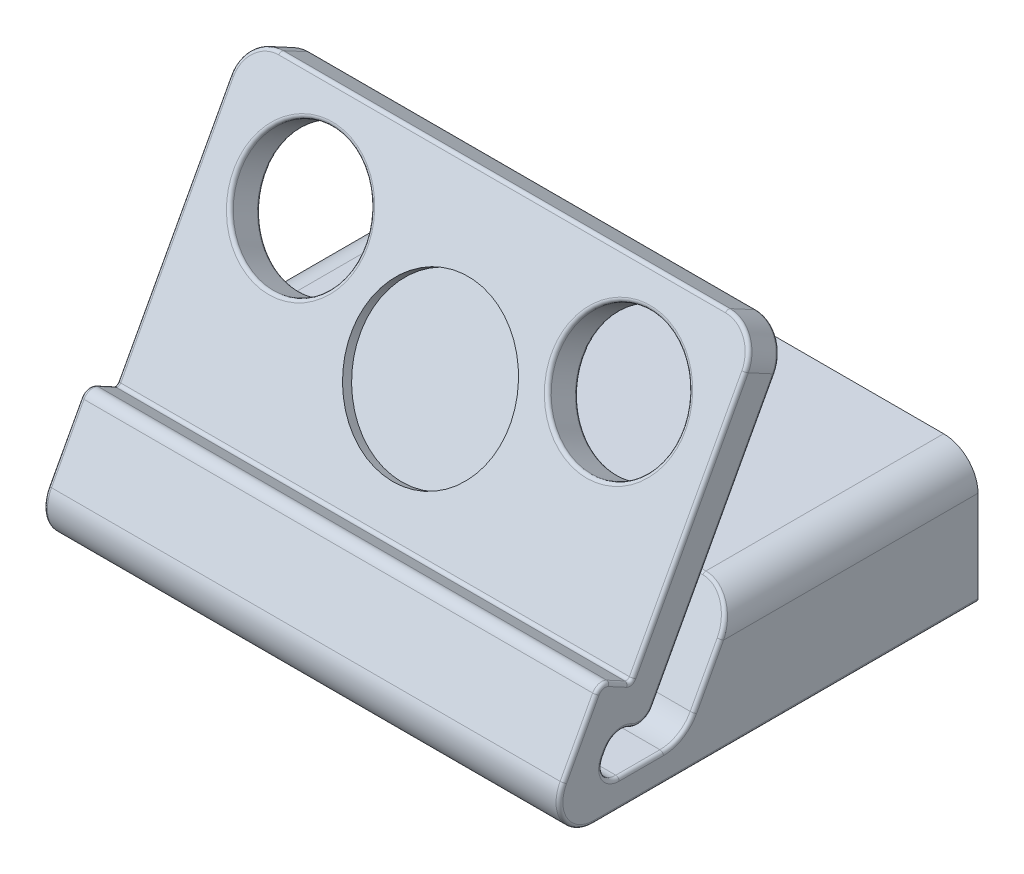
SolidWorks part; units mm, degrees
ref_plane "Front Plane" through (0, 0, 0) normal (0, 0, 1) x (1, 0, 0)
ref_plane "Top Plane" through (0, 0, 0) normal (0, 1, 0) x (1, 0, 0)
ref_plane "Right Plane" through (0, 0, 0) normal (1, 0, 0) x (0, 0, -1)
sketch "Sketch2" plane through (0, 0, 0) normal (1, 0, 0) x (0, 0, -1)
  line L0 (68.9, -29.4084) -> (-59.6419, -29.4084)
  line L1 (-59.6419, -29.4084) -> (-40.8213, 5.5155)
  line L3 (5.934, 71.1961) -> (-32.0182, 0.7714)
  line L4 (-43.865, -21.2117) -> (-16.6838, -21.2117)
  line L5 (-16.6838, -21.2117) -> (-0.8623, 8.147)
  line L6 (-0.8623, 8.147) -> (68.9, 8.147)
  line L7 (68.9, 8.147) -> (68.9, -29.4084)
  line L8 (5.934, 71.1961) -> (14.7371, 66.4521)
  line L9 (14.7371, 66.4521) -> (-27.9592, -12.7757)
  line L10 (-27.9592, -12.7757) -> (-36.7622, -8.0316)
  line L11 (-40.8213, 5.5155) -> (-32.0182, 0.7714)
  line L12 (-36.7622, -8.0316) -> (-43.865, -21.2117)
  dimension "D1" = 10
  dimension "D2" = 10
  dimension "D3" = 10
  dimension "D4" = 80
extrude "Boss-Extrude1" add sketch "Sketch2" against normal blind 150
fillet "Fillet1" radius 10 6 edges at (-150, 8.147, -34.0188) (0, 8.147, -34.0188) (-75, -29.4084, 59.6419) (-150, 68.8241, -10.3355) (0, 68.8241, -10.3355) (-75, -21.2117, 16.6838)
fillet "Fillet2" radius 5 3 edges at (-75, -12.7757, 27.9592) (-75, -8.0316, 36.7622) (-75, -21.2117, 43.865)
fillet "Fillet3" radius 3 1 edges at (-75, 5.5155, 40.8213)
sketch "Sketch3" plane through (0, 13.5451, 25.1344) normal (0, 0.4744, 0.8803) x (1, 0, 0)
  line L0 (-75, 65.4896) -> (-75, -14.5104) construction
  line L1 (-140, 65.4896) -> (-10, 65.4896) construction
  line L2 (-150, -14.5104) -> (0, -14.5104) construction
  circle A0 centre (-75, 20.4896) radius 23.1387
  circle A1 centre (-121.2579, 38.3022) radius 18.5
  circle A2 centre (-28.7421, 38.3022) radius 18.5
extrude "Cut-Extrude1" cut sketch "Sketch3" against normal blind 20 contours A1 | A2 region at (-121.2579, 47.2628, 6.9638) region at (-28.7421, 47.2628, 6.9638)
extrude "Cut-Extrude2" cut sketch "Sketch3<3>" against normal blind 3 contours L0 A0 | A0 L0 region at (-65.1796, 31.5822, 15.4141) region at (-84.8204, 31.5822, 15.4141)
sketch "Sketch3<3>" plane through (0, 13.5451, 25.1344) normal (0, 0.4744, 0.8803) x (1, 0, 0) same geometry as "Sketch3"
ref_plane "Plane1" through (0, 13.0707, 24.2541) normal (0, 0.4744, 0.8803) x (1, 0, 0)
sketch "Sketch4" plane through (0, 13.0707, 24.2541) normal (0, 0.4744, 0.8803) x (1, 0, 0)
  circle A0 centre (-28.7421, 38.3022) radius 18.5 construction
  circle A2 centre (-28.7421, 38.3022) radius 18.5
  circle A4 centre (-121.2579, 38.3022) radius 18.5 construction
  circle A5 centre (-121.2579, 38.3022) radius 18.5
sketch "Sketch5" plane through (0, -29.4084, 0) normal (0, -1, 0) x (1, 0, 0)
  line L1 (-144.1476, -63.2569) -> (-5.2061, -63.2569)
  line L2 (-144.1476, -63.2569) -> (-144.1476, 3.4674)
  line L3 (-144.1476, 3.4674) -> (-5.2061, 3.4674)
  line L4 (-5.2061, -63.2569) -> (-5.2061, 3.4674)
extrude "Cut-Extrude3" cut sketch "Sketch5" against normal blind 10
fillet "Fillet4" radius 1 1 edges at (-75, 0.7714, 32.0182)
fillet "Fillet5" radius 1 4 edges at (-121.2579, 30.9771, 15.7402) (-28.7421, 30.9771, 15.7402) (-28.7421, 58.8044, -10.6157) (-121.2579, 58.8044, -10.6157)
fillet "Fillet6" radius 1 39 edges at (-150, -29.4084, -13.0034) (-150, -24.5348, 51.4792) (-150, -5.8949, 46.9704) (-150, 4.3251, 40.4646) (-150, 2.669, 35.5394) (-150, 1.1682, 32.1371) (-150, 32.0224, 15.1769) (-147.0711, 68.6177, -4.5445) (-75, 71.1961, -5.934) (-2.9289, 68.6177, -4.5445) (0, -29.4084, -13.0034) (0, -24.5348, 51.4792) (0, -5.8949, 46.9704) (0, 4.3251, 40.4646) (0, 2.669, 35.5394) (0, 1.1682, 32.1371) (-2.9289, 5.218, 2.4407) (-75, 8.147, 0.8623) (-147.0711, 5.218, 2.4407) (-150, -8.9044, 10.0514) (-150, -19.7978, 17.5281) (-150, -21.2117, 29.0726) (-150, -18.7749, 39.7837) (-150, -13.1365, 39.5132) (-150, -10.0156, 36.1678) (-150, -10.7917, 28.5536) (-150, 24.6374, 7.7971) (-147.0711, 63.8737, -13.3476) (-75, 66.4521, -14.7371) (-2.9289, 63.8737, -13.3476) (0, 24.6374, 7.7971) (0, -10.7917, 28.5536) (0, -10.0156, 36.1678) (0, -13.1365, 39.5132) (0, -18.7749, 39.7837) (0, -21.2117, 29.0726) (0, -19.7978, 17.5281) (0, 32.0224, 15.1769) (0, -8.9044, 10.0514)
